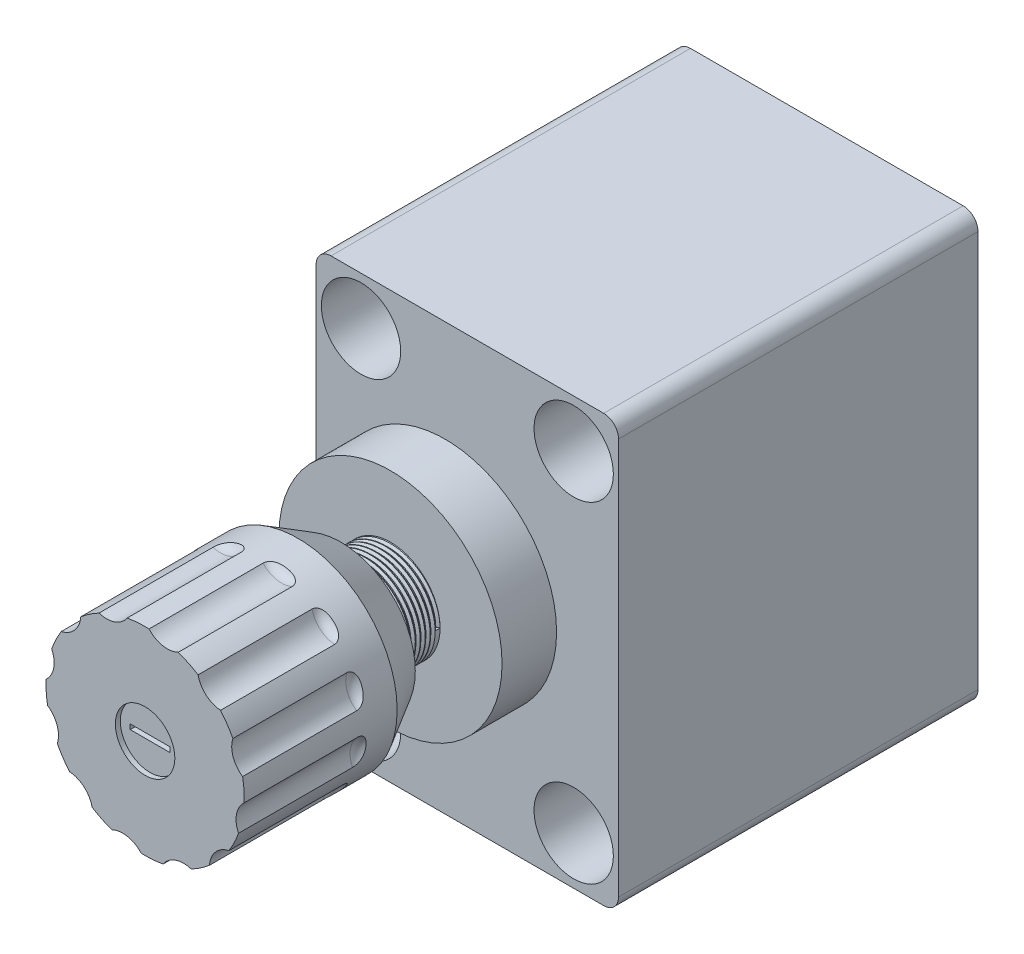
SolidWorks part; units mm, degrees
ref_plane "前视基准面" through (0, 0, 0) normal (0, 0, 1) x (1, 0, 0)
ref_plane "上视基准面" through (0, 0, 0) normal (0, 1, 0) x (1, 0, 0)
ref_plane "右视基准面" through (0, 0, 0) normal (1, 0, 0) x (0, 0, -1)
sketch "草图1" plane through (0, 0, 0) normal (0, 0, 1) x (1, 0, 0)
  line L0 (-34.6132, 0) -> (37.1611, 0) construction
  line L1 (-30.5, 43) -> (30.5, 43)
  line L2 (-30.5, 43) -> (-30.5, -43)
  line L3 (-30.5, -43) -> (30.5, -43)
  line L4 (30.5, 43) -> (30.5, -43)
  line L5 (-30.5, 43) -> (30.5, -43) construction
  line L6 (-30.5, -43) -> (30.5, 43) construction
  line L7 (-21.45, 33.35) -> (21.45, 33.35) construction
  line L8 (-21.45, 33.35) -> (-21.45, -33.35) construction
  line L9 (-21.45, -33.35) -> (21.45, -33.35) construction
  line L10 (21.45, 33.35) -> (21.45, -33.35) construction
  line L11 (-21.45, 33.35) -> (21.45, -33.35) construction
  line L12 (-21.45, -33.35) -> (21.45, 33.35) construction
  circle A0 centre (-21.45, 33.35) radius 5
  circle A1 centre (21.45, 33.35) radius 5
  circle A2 centre (21.45, -33.35) radius 5
  circle A3 centre (-21.45, -33.35) radius 5
  circle A4 centre (-14.35, 0.05) radius 6
  circle A5 centre (14.25, 0.05) radius 6
  circle A6 centre (10.35, -33.35) radius 3.75
  point P0 (0, 0)
  point P6 (0, 0)
  dimension "D3" = 10
  dimension "D10" = 66.7
  dimension "D9" = 12
  dimension "D12" = 7.5
  dimension "D1" = 61
  dimension "D2" = 86
  dimension "D4" = 42.9
  dimension "D5" = 66.7
  dimension "D6" = 7.1
  dimension "D7" = 35.7
  dimension "D8" = 33.3
  dimension "D11" = 31.8
extrude "凸台-拉伸1" add sketch "草图1" against normal blind 72.5
sketch "草图3" plane through (0, 0, 0) normal (0, 0, 1) x (1, 0, 0)
  circle A1 centre (-14.35, 0.05) radius 6 construction
  circle A3 centre (-14.35, 0.05) radius 6
  circle A5 centre (14.25, 0.05) radius 6 construction
  circle A6 centre (14.25, 0.05) radius 6
  circle A7 centre (10.35, -33.35) radius 3.75 construction
  circle A8 centre (10.35, -33.35) radius 3.75
extrude "凸台-拉伸2" add sketch "草图3" against normal blind 30
sketch "草图2" plane through (0, 0, 0) normal (0, 0, 1) x (1, 0, 0)
  circle A0 centre (-21.45, 33.35) radius 8
  circle A1 centre (-21.45, -33.35) radius 8
  circle A2 centre (21.45, -33.35) radius 8
  circle A3 centre (21.45, 33.35) radius 8
  dimension "D1" = 16
extrude "切除-拉伸1" cut sketch "草图2" against normal blind 12
sketch "草图5" plane through (0, 0, 0) normal (0, 1, 0) x (0, 0, -1)
  line L0 (-36.7448, 0) -> (74.691, 0) construction
  line L1 (0, 66.5114) -> (0, -66.3947) construction
  line L2 (-85.2062, 4.5) -> (80.642, 4.5) construction
  line L3 (72.5, -30.5) -> (0, -30.5) construction
  line L4 (0, -18) -> (-11, -18)
  line L5 (-11, -18) -> (-11, -5.5)
  line L6 (-11, -5.5) -> (-21, -5.5)
  line L7 (-21, -5.5) -> (-21, -10.5)
  line L8 (-29.6603, -15.5) -> (-60.5, -15.5)
  line L9 (-60.5, -15.5) -> (-60.5, 4.5)
  line L11 (0, -18) -> (0, 4.5)
  line L12 (0, 4.5) -> (-60.5, 4.5)
  line L13 (-21, -10.5) -> (-29.6603, -15.5)
  line L14 (72.5, -27.5) -> (72.5, 27.5) construction
  dimension "D1" = 35
  dimension "D2" = 22.5
  dimension "D3" = 20
  dimension "D4" = 133
  dimension "D5" = 11
  dimension "D6" = 10
  dimension "D7" = 15
  dimension "D8" = 10
  dimension "D9" = 30
revolve "旋转1" add sketch "草图5" angle 360 about L2
fillet "圆角1" radius 3 4 edges at (-30.5, -43, -36.25) (30.5, -43, -36.25) (-30.5, 43, -36.25) (30.5, 43, -36.25)
sketch "草图7" plane through (0, 0, 60.5) normal (0, 0, 1) x (1, 0, 0)
  circle A0 centre (-4.5, 0) radius 6
  dimension "D1" = 12
extrude "切除-拉伸2" cut sketch "草图7" against normal blind 1
sketch "草图8" plane through (0, 0, 59.5) normal (0, 0, 1) x (1, 0, 0)
  line L0 (-10.5, 0) -> (1.5, 0) construction
  line L2 (-8.5, 0.5) -> (-0.5, 0.5)
  line L3 (-8.5, 0.5) -> (-8.5, -0.5)
  line L4 (-8.5, -0.5) -> (-0.5, -0.5)
  line L5 (-0.5, 0.5) -> (-0.5, -0.5)
  line L6 (-8.5, 0.5) -> (-0.5, -0.5) construction
  line L7 (-8.5, -0.5) -> (-0.5, 0.5) construction
  circle A0 centre (-4.5, 0) radius 6 construction
  point P5 (-4.5, 0)
  dimension "D1" = 1
  dimension "D2" = 8
extrude "切除-拉伸3" cut sketch "草图8" against normal blind 2
thread "螺纹线1" pitch 1 method cut profile "螺纹线轮廓1" start angle 0, offset 0, length 15, pitch 1, diameter 20
ref_plane "基准面1" through (5.5, 0, 11) normal (0, -1, 0) x (1, 0, 0)
sketch "螺纹线轮廓1" plane through (5.5, 0, 11) normal (0, -1, 0) x (1, 0, 0)
  line L0 (0, 0) -> (0, 1) construction
  line L11 (0, 0) -> (0, 0.875)
  line L12 (0, 0.875) -> (-0.5413, 0.5625)
  line L13 (-0.5413, 0.5625) -> (-0.5413, 0.3125)
  line L15 (-0.5413, 0.3125) -> (0, 0)
  line L17 (-0.5413, 0.4375) -> (0, 0.4375) construction
  point P2 (0, 0)
  dimension "Pitch" = 1
  dimension "Profile_Angle" = 60
  dimension "Profile_Land" = 0.25
  dimension "Profile_Height" = 0.5413
sketch "草图9" plane through (0, 0, 60.5) normal (0, 0, 1) x (1, 0, 0)
  line L0 (0, 19.1882) -> (0, -34.8382) construction
  line L1 (-34.3619, 0) -> (33.3412, 0) construction
  arc A0 (-3.7029, 19.9841) -> (2.1886, 18.8484) centre (0, 23.3439) ccw
  circle A1 centre (-4.5, 0) radius 20 construction
  arc A2 (-24.5, 0) -> (15.5, 0) centre (-4.5, 0) ccw
  arc A3 (2.1886, 18.8484) -> (-3.7029, 19.9841) centre (-4.5, 0) ccw
  circle M2 centre (-4.5, 0) radius 20
  dimension "D2" = 5
  dimension "D1" = 6
extrude "切除-拉伸4" cut sketch "草图9" against normal blind 25 contours A0 M2 region at (-0.8166, 19.108, 60.5)
fillet "圆角2" radius 2 1 edges at (-0.9464, 18.4343, 35.5)
pattern_circular "阵列(圆周)1" count 12 over 360 about axis through (-4.5, 0, 29.6603) along (0, 0, 1) of "切除-拉伸4", "圆角2"
